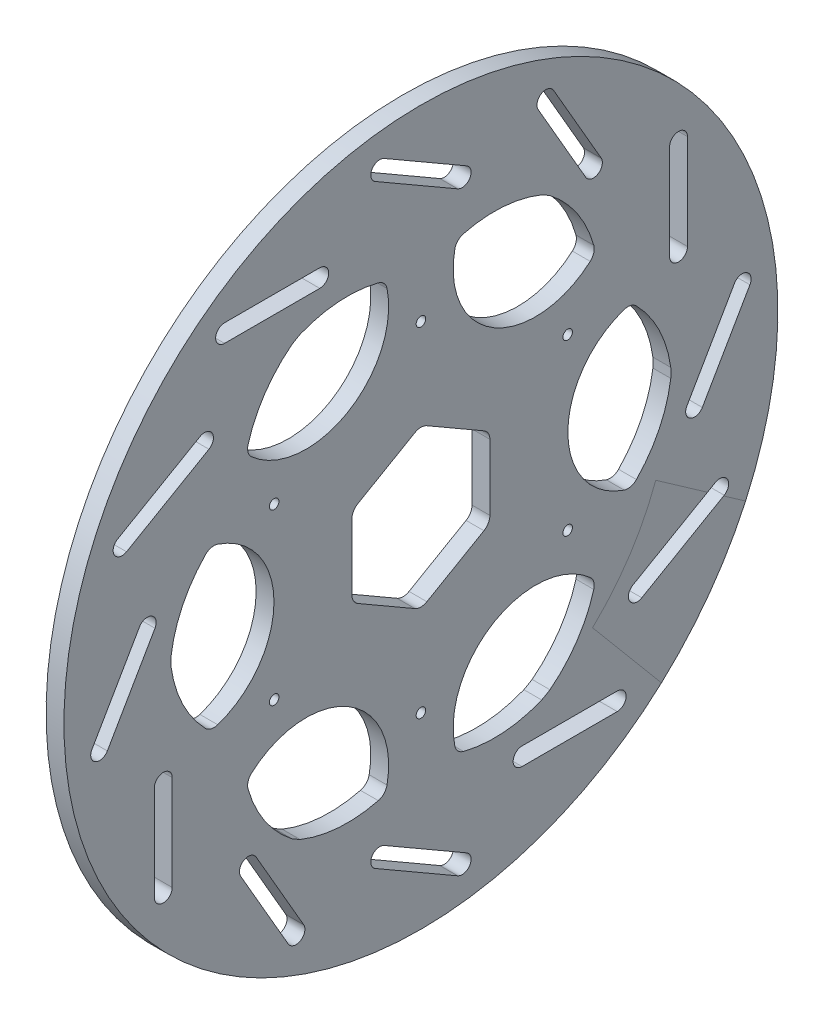
SolidWorks part; units mm, degrees
material "Gray Cast Iron"
ref_plane "X-Y Datum" through (0, 0, 0) normal (0, 0, 1) x (1, 0, 0)
ref_plane "X-Z Datum" through (0, 0, 0) normal (0, 1, 0) x (1, 0, 0)
ref_plane "Y-Z Datum" through (0, 0, 0) normal (1, 0, 0) x (0, 0, -1)
sketch "Sketch1" plane through (0, 0, 0) normal (1, 0, 0) x (0, 0, -1)
  circle A0 centre (0, 0) radius 95.25
  circle A1 centre (0, 0) radius 66.675
  dimension "D1" = 190.5
  dimension "D2" = 133.35
extrude "Main Rotor" add sketch "Sketch1" along normal blind 4.7625
sketch "Sketch2" plane through (4.7625, 0, 0) normal (1, 0, 0) x (0, 0, -1)
  line L0 (0, 0) -> (-50000, 0) construction
  line L1 (-85.725, -10.9985) -> (-73.025, 10.9985) construction
  line L2 (-87.7872, -9.8079) -> (-75.0872, 12.1891)
  line L3 (-83.6628, -12.1891) -> (-70.9628, 9.8079)
  line L4 (-79.7393, 33.3375) -> (-57.7422, 46.0375) construction
  line L5 (-80.9299, 35.3997) -> (-58.9329, 48.0997)
  line L6 (-78.5487, 31.2753) -> (-56.5516, 43.9753)
  line L7 (-52.3875, 68.7408) -> (-26.9875, 68.7408) construction
  line L8 (-52.3875, 71.122) -> (-26.9875, 71.122)
  line L9 (-52.3875, 66.3595) -> (-26.9875, 66.3595)
  line L10 (-10.9985, 85.725) -> (10.9985, 73.025) construction
  line L11 (-9.8079, 87.7872) -> (12.1891, 75.0872)
  line L12 (-12.1891, 83.6628) -> (9.8079, 70.9628)
  line L13 (33.3375, 79.7393) -> (46.0375, 57.7422) construction
  line L14 (35.3997, 80.9299) -> (48.0997, 58.9329)
  line L15 (31.2753, 78.5487) -> (43.9753, 56.5516)
  line L16 (68.7408, 52.3875) -> (68.7408, 26.9875) construction
  line L17 (71.122, 52.3875) -> (71.122, 26.9875)
  line L18 (66.3595, 52.3875) -> (66.3595, 26.9875)
  line L19 (85.725, 10.9985) -> (73.025, -10.9985) construction
  line L20 (87.7872, 9.8079) -> (75.0872, -12.1891)
  line L21 (83.6628, 12.1891) -> (70.9628, -9.8079)
  line L22 (79.7393, -33.3375) -> (57.7422, -46.0375) construction
  line L23 (80.9299, -35.3997) -> (58.9329, -48.0997)
  line L24 (78.5487, -31.2753) -> (56.5516, -43.9753)
  line L25 (52.3875, -68.7408) -> (26.9875, -68.7408) construction
  line L26 (52.3875, -71.122) -> (26.9875, -71.122)
  line L27 (52.3875, -66.3595) -> (26.9875, -66.3595)
  line L28 (10.9985, -85.725) -> (-10.9985, -73.025) construction
  line L29 (9.8079, -87.7872) -> (-12.1891, -75.0872)
  line L30 (12.1891, -83.6628) -> (-9.8079, -70.9628)
  line L31 (-33.3375, -79.7393) -> (-46.0375, -57.7422) construction
  line L32 (-35.3997, -80.9299) -> (-48.0997, -58.9329)
  line L33 (-31.2753, -78.5487) -> (-43.9753, -56.5516)
  line L34 (-68.7408, -52.3875) -> (-68.7408, -26.9875) construction
  line L35 (-71.122, -52.3875) -> (-71.122, -26.9875)
  line L36 (-66.3595, -52.3875) -> (-66.3595, -26.9875)
  arc A0 (-87.7872, -9.8079) -> (-83.6628, -12.1891) centre (-85.725, -10.9985) ccw
  arc A1 (-70.9628, 9.8079) -> (-75.0872, 12.1891) centre (-73.025, 10.9985) ccw
  circle A2 centre (0, 0) radius 95.25 construction
  arc A3 (-80.9299, 35.3997) -> (-78.5487, 31.2753) centre (-79.7393, 33.3375) ccw
  arc A4 (-56.5516, 43.9753) -> (-58.9329, 48.0997) centre (-57.7422, 46.0375) ccw
  arc A5 (-52.3875, 71.122) -> (-52.3875, 66.3595) centre (-52.3875, 68.7408) ccw
  arc A6 (-26.9875, 66.3595) -> (-26.9875, 71.122) centre (-26.9875, 68.7408) ccw
  arc A7 (-9.8079, 87.7872) -> (-12.1891, 83.6628) centre (-10.9985, 85.725) ccw
  arc A8 (9.8079, 70.9628) -> (12.1891, 75.0872) centre (10.9985, 73.025) ccw
  arc A9 (35.3997, 80.9299) -> (31.2753, 78.5487) centre (33.3375, 79.7393) ccw
  arc A10 (43.9753, 56.5516) -> (48.0997, 58.9329) centre (46.0375, 57.7422) ccw
  arc A11 (71.122, 52.3875) -> (66.3595, 52.3875) centre (68.7408, 52.3875) ccw
  arc A12 (66.3595, 26.9875) -> (71.122, 26.9875) centre (68.7408, 26.9875) ccw
  arc A13 (87.7872, 9.8079) -> (83.6628, 12.1891) centre (85.725, 10.9985) ccw
  arc A14 (70.9628, -9.8079) -> (75.0872, -12.1891) centre (73.025, -10.9985) ccw
  arc A15 (80.9299, -35.3997) -> (78.5487, -31.2753) centre (79.7393, -33.3375) ccw
  arc A16 (56.5516, -43.9753) -> (58.9329, -48.0997) centre (57.7422, -46.0375) ccw
  arc A17 (52.3875, -71.122) -> (52.3875, -66.3595) centre (52.3875, -68.7408) ccw
  arc A18 (26.9875, -66.3595) -> (26.9875, -71.122) centre (26.9875, -68.7408) ccw
  arc A19 (9.8079, -87.7872) -> (12.1891, -83.6628) centre (10.9985, -85.725) ccw
  arc A20 (-9.8079, -70.9628) -> (-12.1891, -75.0872) centre (-10.9985, -73.025) ccw
  arc A21 (-35.3997, -80.9299) -> (-31.2753, -78.5487) centre (-33.3375, -79.7393) ccw
  arc A22 (-43.9753, -56.5516) -> (-48.0997, -58.9329) centre (-46.0375, -57.7422) ccw
  arc A23 (-71.122, -52.3875) -> (-66.3595, -52.3875) centre (-68.7408, -52.3875) ccw
  arc A24 (-66.3595, -26.9875) -> (-71.122, -26.9875) centre (-68.7408, -26.9875) ccw
  point P5 (-79.375, 0)
  point P16 (-68.7408, 39.6875)
  point P23 (-39.6875, 68.7408)
  point P30 (0, 79.375)
  point P37 (39.6875, 68.7408)
  point P44 (68.7408, 39.6875)
  point P51 (79.375, 0)
  point P58 (68.7408, -39.6875)
  point P65 (39.6875, -68.7408)
  point P72 (0, -79.375)
  point P79 (-39.6875, -68.7408)
  point P86 (-68.7408, -39.6875)
  point P91 (0, 0)
  dimension "D1" = 60
  dimension "D2" = 79.375
  dimension "D3" = 25.4
  dimension "D4" = 4.7625
  dimension "D5" = 12
extrude "Cut Slots" cut sketch "Sketch2" against normal through all
sketch "Sketch3" plane through (4.7625, 0, 0) normal (1, 0, 0) x (0, 0, -1)
  line L0 (0, 0) -> (-43301.2702, 25000) construction
  line L1 (0, 21.2491) -> (-18.4023, 10.6246)
  line L2 (-18.4023, 10.6246) -> (-18.4023, -10.6246)
  line L3 (-18.4023, -10.6246) -> (0, -21.2491)
  line L4 (0, -21.2491) -> (18.4023, -10.6246)
  line L5 (18.4023, -10.6246) -> (18.4023, 10.6246)
  line L6 (18.4023, 10.6246) -> (0, 21.2491)
  line L7 (0, 0) -> (43301.2702, 25000) construction
  line L8 (0, 0) -> (0, 50000) construction
  line L12 (9.525, -59.2994) -> (-9.525, -59.2994) construction
  line L17 (-30.6007, -53.002) -> (24969.3838, 43248.2414) construction
  line L18 (-60.783, 0) -> (49939.217, 0) construction
  line L19 (0, 0) -> (-25000, 43301.2702) construction
  circle A1 centre (0, 0) radius 66.675 construction
  arc A7 (-9.525, -59.2994) -> (-32.2316, -58.3668) centre (-19.5921, -27.5182) cw
  arc A10 (9.525, -59.2994) -> (32.2316, -58.3668) centre (19.5921, -27.5182) ccw
  arc A19 (-19.6024, -33.9524) -> (-9.525, -59.2994) centre (-30.6006, -53.0019) cw
  arc A26 (34.4313, -57.0968) -> (66.6629, -1.27) centre (0, 0) ccw
  arc A28 (19.6024, -33.9524) -> (9.525, -59.2994) centre (30.6006, -53.0019) ccw
  arc A30 (-46.5923, -37.8986) -> (-34.4313, -57.0968) centre (-14.0354, -30.7264) ccw
  arc A31 (-19.6024, -33.9524) -> (-46.5923, -37.8986) centre (-30.6006, -53.0019) ccw
  arc A32 (-39.2049, 0) -> (-56.1173, -21.4008) centre (-61.2013, 0) cw
  arc A33 (-56.1173, -21.4008) -> (-66.6629, -1.27) centre (-33.6275, 3.2082) cw
  arc A34 (-56.1173, 21.4008) -> (-66.6629, 1.27) centre (-33.6275, -3.2082) ccw
  arc A36 (-32.2316, -58.3668) -> (32.2316, -58.3668) centre (0, 0) ccw
  arc A44 (-39.2049, 0) -> (-56.1173, 21.4008) centre (-61.2013, 0) ccw
  arc A45 (-19.6025, 33.9524) -> (-46.5923, 37.8986) centre (-30.6007, 53.0019) cw
  arc A46 (-46.5923, 37.8986) -> (-34.4313, 57.0968) centre (-14.0354, 30.7264) cw
  arc A47 (-9.525, 59.2994) -> (-32.2316, 58.3668) centre (-19.5921, 27.5182) ccw
  arc A48 (-19.6025, 33.9524) -> (-9.525, 59.2994) centre (-30.6007, 53.0019) ccw
  arc A49 (19.6024, 33.9524) -> (9.525, 59.2994) centre (30.6006, 53.0019) cw
  arc A50 (9.525, 59.2994) -> (32.2316, 58.3668) centre (19.5921, 27.5182) cw
  arc A51 (46.5923, 37.8986) -> (34.4313, 57.0968) centre (14.0354, 30.7264) ccw
  arc A52 (19.6024, 33.9524) -> (46.5923, 37.8986) centre (30.6006, 53.0019) ccw
  arc A53 (39.2049, 0) -> (56.1173, 21.4008) centre (61.2013, 0) cw
  arc A54 (56.1173, 21.4008) -> (66.6629, 1.27) centre (33.6275, -3.2082) cw
  arc A55 (56.1173, -21.4008) -> (66.6629, -1.27) centre (33.6275, 3.2082) ccw
  arc A56 (39.2049, 0) -> (56.1173, -21.4008) centre (61.2013, 0) ccw
  arc A57 (19.6024, -33.9524) -> (46.5923, -37.8986) centre (30.6007, -53.0019) cw
  arc A58 (46.5923, -37.8986) -> (34.4313, -57.0968) centre (14.0354, -30.7264) cw
  arc A60 (-66.6629, -1.27) -> (-34.4313, -57.0968) centre (0, 0) ccw
  arc A62 (-34.4313, 57.0968) -> (-66.6629, 1.27) centre (0, 0) ccw
  arc A64 (32.2316, 58.3668) -> (-32.2316, 58.3668) centre (0, 0) ccw
  arc A66 (66.6629, 1.27) -> (34.4313, 57.0968) centre (0, 0) ccw
  point P34 (0, -59.2994)
  point P35 (-9.2012, 15.9369)
  point P124 (0, 0)
  dimension "D2" = 42.799
  dimension "D7" = 1.27
  dimension "D8" = 33.3375
  dimension "D9" = 21.9964
  dimension "D1" = 36.8046
  dimension "D3" = 6
  dimension "D6" = 19.05
extrude "Boss-Extrude2" add sketch "Sketch3" against normal up to surface (4.7625 mm away) up to face at (0, -68.7408, -39.6875)
fillet "Fillet1" radius 3.175 6 edges at (2.3813, 10.6246, -18.4023) (2.3813, -10.6246, -18.4023) (2.3813, -21.2491, 0) (2.3813, -10.6246, 18.4023) (2.3813, 10.6246, 18.4023) (2.3813, 21.2491, 0)
fillet "Fillet2" radius 3.175 12 edges at (2.3813, 59.2994, -9.525) (2.3813, 37.8986, -46.5923) (2.3813, 21.4008, -56.1173) (2.3813, -21.4008, -56.1173) (2.3813, -37.8986, -46.5923) (2.3813, -59.2994, -9.525) (2.3813, -59.2994, 9.525) (2.3813, -37.8986, 46.5923) (2.3813, -21.4008, 56.1173) (2.3813, 21.4008, 56.1173) (2.3813, 37.8986, 46.5923) (2.3813, 59.2994, 9.525)
sketch "Sketch4" plane through (0, 0, 0) normal (-1, 0, 0) x (0, 0, 1)
  circle A0 centre (0, 45.212) radius 1.27
  circle A1 centre (39.1547, 22.606) radius 1.27
  circle A2 centre (39.1547, -22.606) radius 1.27
  circle A3 centre (0, -45.212) radius 1.27
  circle A4 centre (-39.1547, -22.606) radius 1.27
  circle A5 centre (-39.1547, 22.606) radius 1.27
  point P16 (0, 0)
  dimension "D1" = 45.212
  dimension "D2" = 2.54
  dimension "D3" = 6
extrude "Cut-Extrude2" cut sketch "Sketch4" against normal through all
sketch "Sketch5" plane through (4.7625, 0, 0) normal (1, 0, 0) x (0, 0, -1)
  line L0 (0, 0) -> (-50000, 0) construction
  line L1 (0, 0) -> (-46984.631, 17101.0072) construction
  line L2 (62.654, -22.8042) -> (86.6311, -39.5931)
  line L3 (45.7933, -48.4616) -> (64.1833, -70.378)
  circle A0 centre (0, 0) radius 95.25 construction
  circle A1 centre (0, 0) radius 66.675 construction
  arc A2 (64.1833, -70.378) -> (86.6311, -39.5931) centre (0, 0) ccw
  arc A3 (45.7933, -48.4616) -> (62.654, -22.8042) centre (0, 0) ccw
  dimension "D1" = 20
  dimension "D2" = 15
  dimension "D3" = 15
  dimension "D4" = 38.1
split line "Split Line1"
ref_axis "Axis1" through (5.0006, 0, 0) along (-1, 0, 0)
